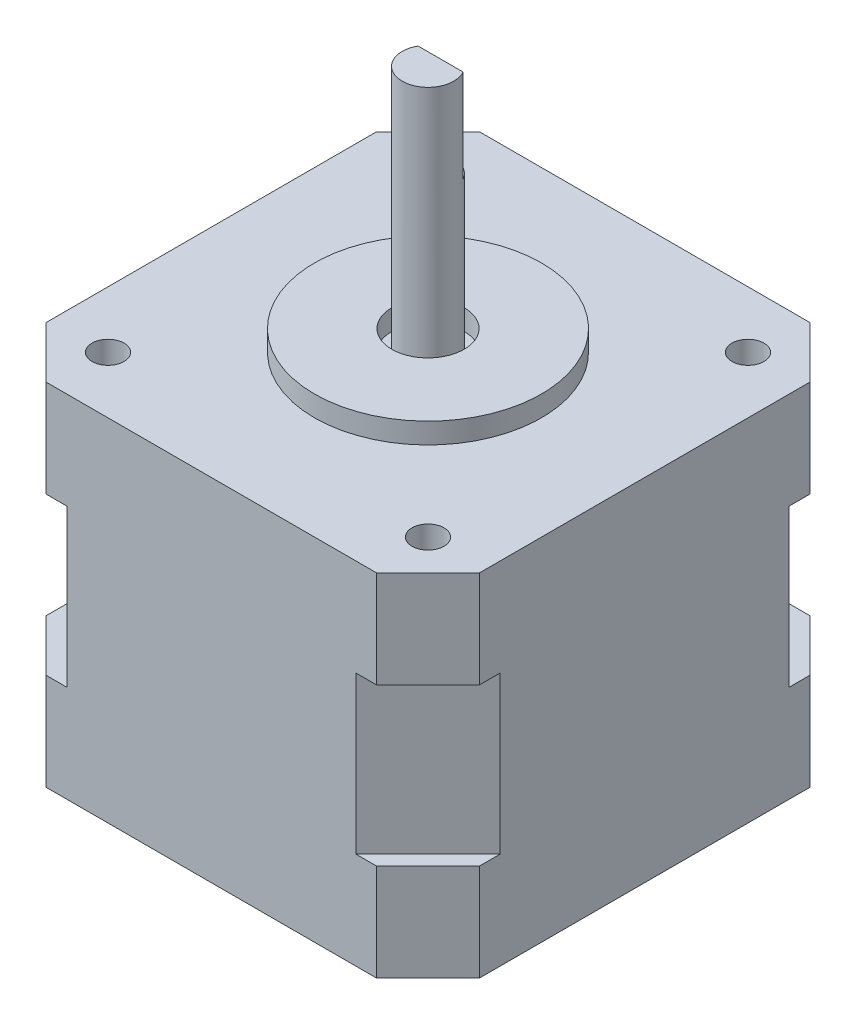
SolidWorks part; units mm, degrees
ref_plane "Front Plane" through (0, 0, 0) normal (0, 0, 1) x (1, 0, 0)
ref_plane "Top Plane" through (0, 0, 0) normal (0, 1, 0) x (1, 0, 0)
ref_plane "Right Plane" through (0, 0, 0) normal (1, 0, 0) x (0, 0, -1)
sketch "Sketch4" plane through (0, 0, 0) normal (0, 1, 0) x (1, 0, 0)
  line L1 (-21, -21) -> (21, -21)
  line L2 (-21, -21) -> (-21, 21)
  line L3 (-21, 21) -> (21, 21)
  line L4 (21, -21) -> (21, 21)
  line L5 (-21, -21) -> (21, 21) construction
  line L6 (-21, 21) -> (21, -21) construction
  point P0 (0, 0)
  dimension "D1" = 42
  dimension "D2" = 42
extrude "Bottom" add sketch "Sketch4" along normal blind 9.4 contours L2 L3 L4 L1
sketch "Sketch6" plane through (0, 9.4, 0) normal (0, 1, 0) x (1, 0, 0)
  line L0 (-21, -14) -> (-14, -21)
  line L1 (-14, -21) -> (14, -21)
  line L2 (-21, -14) -> (-21, 14)
  line L3 (-14, 21) -> (14, 21)
  line L4 (21, -14) -> (21, 14)
  line L5 (-21, -21) -> (21, 21) construction
  line L6 (-21, 21) -> (21, -21) construction
  line L7 (-21, 14) -> (-14, 21)
  line L8 (14, 21) -> (21, 14)
  line L9 (14, -21) -> (21, -14)
  point P0 (0, 0)
  dimension "D1" = 42
  dimension "D2" = 42
extrude "Middle" add sketch "Sketch6" along normal blind 15.2
sketch "Sketch8" plane through (0, 24.6, 0) normal (0, 1, 0) x (1, 0, 0)
  line L1 (-21, -21) -> (21, -21)
  line L2 (-21, -21) -> (-21, 21)
  line L3 (-21, 21) -> (21, 21)
  line L4 (21, -21) -> (21, 21)
  line L5 (-21, -21) -> (21, 21) construction
  line L6 (-21, 21) -> (21, -21) construction
  point P0 (0, 0)
  dimension "D1" = 42
  dimension "D2" = 42
extrude "Top" add sketch "Sketch8" along normal blind 9.4
chamfer "Chamfer1" distance 5 angle 45 8 edges at (21, 4.7, -21) (21, 29.3, -21) (-21, 4.7, 21) (21, 4.7, 21) (21, 29.3, 21) (-21, 29.3, 21) (-21, 4.7, -21) (-21, 29.3, -21)
sketch "Sketch9" plane through (0, 34, 0) normal (0, 1, 0) x (1, 0, 0)
  circle A0 centre (0, 0) radius 11
  circle A1 centre (0, 0) radius 3.5
  dimension "D1" = 22
  dimension "D2" = 7
extrude "Ring" add sketch "Sketch9" along normal blind 2 contours A0 | A1
sketch "Sketch10" plane through (0, 34, 0) normal (0, 1, 0) x (1, 0, 0)
  circle A0 centre (0, 0) radius 2.5
  dimension "D1" = 5
extrude "Shaft" add sketch "Sketch10" along normal blind 24
sketch "Sketch11" plane through (0, 0, 0) normal (1, 0, 0) x (0, 0, -1)
  line L0 (2.5, 34) -> (-2.5, 34) construction
  line L1 (3.4584, 73.2425) -> (1.2188, 73.2425)
  line L2 (3.4584, 73.2425) -> (3.4584, 49)
  line L3 (3.4584, 49) -> (1.2188, 49)
  line L4 (1.2188, 73.2425) -> (1.2188, 49)
  dimension "D1" = 15
extrude "Cut-Extrude3" cut sketch "Sketch11" against normal blind 5 and the other way blind 5
sketch "Sketch12" plane through (0, 34, 0) normal (0, 1, 0) x (1, 0, 0)
  line L0 (0, 0) -> (0, 23.6682) construction
  line L1 (0, 0) -> (27.1799, 0) construction
  circle A0 centre (15.5, -15.5) radius 1.55
  circle A1 centre (-15.5, -15.5) radius 1.55
  circle A2 centre (-15.5, 15.5) radius 1.55
  circle A3 centre (15.5, 15.5) radius 1.55
  dimension "D1" = 3.1
  dimension "D4" = 31
  dimension "D5" = 31
  dimension "D6" = 15.5
  dimension "D7" = 15.5
  dimension "D8" = 15.5
  dimension "D2" = 2
  dimension "D3" = 2
extrude "Cut-Extrude4" cut sketch "Sketch12" against normal blind 4.5 contours A0 | A1 | A2 | A3
sketch "Sketch13" plane through (0, 0, 0) normal (0, 0, 1) x (1, 0, 0)
  line L0 (0, 0) -> (0, 63.2226) construction
  line L1 (-16, 0) -> (16, 0) construction
